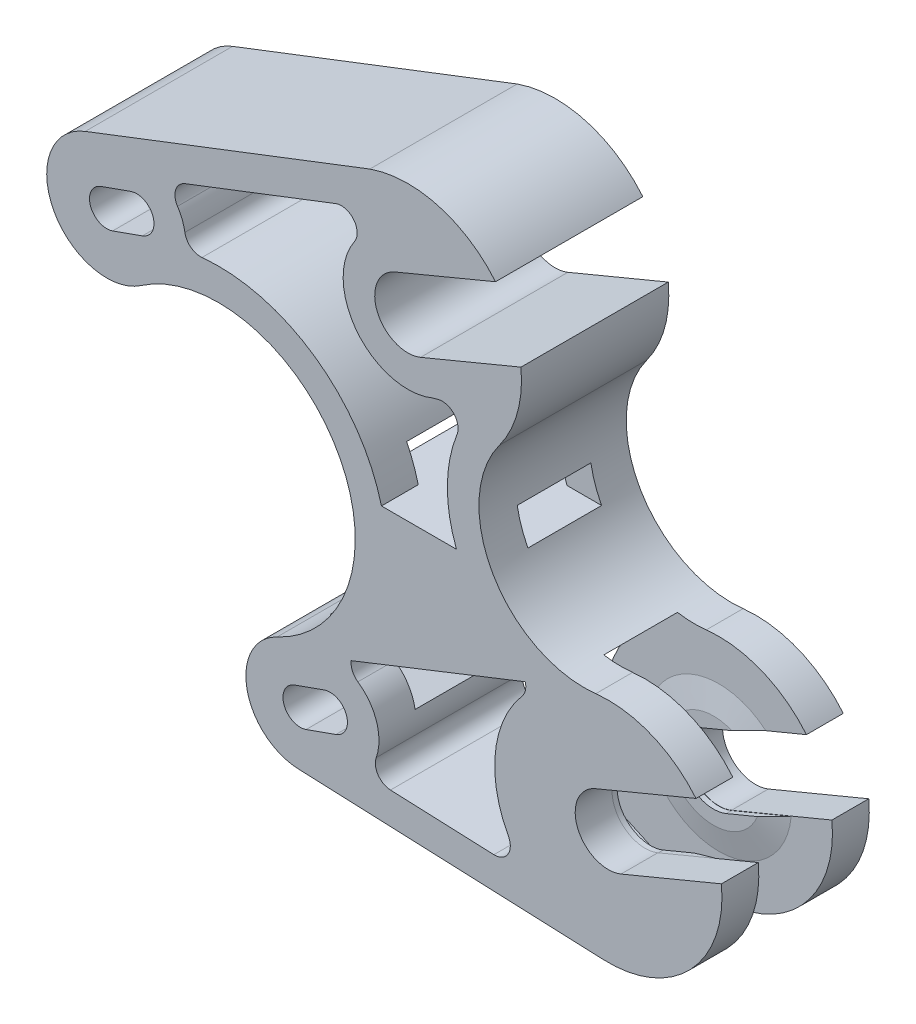
SolidWorks part; units mm, degrees
material "ABS"
ref_plane "Front Plane" through (0, 0, 0) normal (0, 0, 1) x (1, 0, 0)
ref_plane "Top Plane" through (0, 0, 0) normal (0, 1, 0) x (1, 0, 0)
ref_plane "Right Plane" through (0, 0, 0) normal (1, 0, 0) x (0, 0, -1)
ref_plane "Plane1" through (0, 0, 7) normal (0, 0, 1) x (1, 0, 0)
sketch "Sketch1" plane through (0, 0, 0) normal (0, 0, 1) x (1, 0, 0)
  line L0 (18, 21) -> (37.0525, -11.9999) construction
  line L1 (15.9217, 9.1924) -> (-6.382, 15.1686) construction
  line L2 (-9.1924, 15.9217) -> (-15.9217, -9.1924) construction
  line L3 (-15.9217, -9.1924) -> (7.5986, -15.4946) construction
  line L4 (9.1924, -15.9217) -> (9.6194, -14.3279) construction
  line L5 (0, 0) -> (50.7667, 0) construction
  line L6 (0, 0) -> (-9.1924, 15.9217) construction
  line L7 (14.3863, 31.1775) -> (-12.6613, 20.7525)
  line L9 (0, 0) -> (9.1924, -15.9217) construction
  line L10 (10.0538, -13.8649) -> (7.2268, -14.8687)
  line L11 (16.7912, 23.9088) -> (26.3307, 27.8731)
  line L12 (19.2088, 18.0912) -> (28.7483, 22.0554)
  line L13 (35.8437, -9.0911) -> (45.3832, -5.1268)
  line L14 (38.2613, -14.9087) -> (47.8008, -10.9445)
  line L15 (-11.158, 16.9747) -> (-8.3309, 17.9785)
  line L16 (-10.0538, 13.8649) -> (-7.2268, 14.8687)
  line L17 (-7.5986, 15.4946) -> (-9.1924, 15.9217) construction
  line L18 (7.5655, -21.5918) -> (36.607, -22.7907)
  line L19 (11.158, -16.9747) -> (8.3309, -17.9785)
  line L20 (9.7109, -13.9867) -> (15.9217, 9.1924) construction
  arc A0 (5.5647, -11.7488) -> (-7.3672, 10.711) centre (0, 0) ccw
  arc A1 (16.7912, 23.9088) -> (19.2088, 18.0912) centre (18, 21) ccw
  arc A2 (-11.158, 16.9747) -> (-10.0538, 13.8649) centre (-10.6059, 15.4198) ccw
  arc A3 (8.3309, -17.9785) -> (7.2268, -14.8687) centre (7.7788, -16.4236) cw
  arc A4 (-12.6613, 20.7525) -> (-7.3672, 10.711) centre (-10.6059, 15.4198) ccw
  arc A5 (26.6989, 14.5993) -> (28.7483, 22.0554) centre (18, 21) ccw
  arc A6 (35.8437, -9.0911) -> (38.2613, -14.9087) centre (37.0525, -11.9999) ccw
  arc A7 (5.5647, -11.7488) -> (7.5655, -21.5918) centre (7.7788, -16.4236) ccw
  arc A8 (45.3832, -5.1268) -> (35.8587, -1.2661) centre (37.0525, -11.9999) ccw
  arc A9 (36.607, -22.7907) -> (47.8008, -10.9445) centre (37.0525, -11.9999) ccw
  arc A12 (26.6989, 14.5993) -> (35.8587, -1.2661) centre (34.7534, 8.6726) ccw
  arc A13 (26.3307, 27.8731) -> (14.3863, 31.1775) centre (18, 21) ccw
  arc A14 (-8.3309, 17.9785) -> (-7.2268, 14.8687) centre (-7.7788, 16.4236) cw
  arc A15 (10.0538, -13.8649) -> (11.158, -16.9747) centre (10.6059, -15.4198) cw
  dimension "D1" = 26
  dimension "D2" = 3
  dimension "D3" = 6.3
  dimension "D10" = 10.8
  dimension "D11" = 10
  dimension "D4" = 21
  dimension "D5" = 38.105
  dimension "D6" = 60
  dimension "D7" = 18
  dimension "D8" = 15
  dimension "D14" = 3
extrude "Boss-Extrude1" add sketch "Sketch1" along normal blind 14
sketch "Sketch3" plane through (0, 0, 7) normal (0, 0, 1) x (1, 0, 0)
  line L0 (0, 7) -> (37.0525, 7)
  line L1 (-2.9117, -6.3657) -> (32.2689, -22.4578)
  line L2 (5.7446, 4) -> (37.0525, 4)
  line L3 (3.5601, -6.0271) -> (26.4728, -16.5076)
  line L4 (37.0525, 4) -> (37.0525, 7)
  line L5 (0, 4) -> (23.3288, 4) construction
  line L6 (-1.6639, -3.6375) -> (33.5168, -19.7296) construction
  line L7 (0, 7) -> (23.3288, 7) construction
  circle A0 centre (37.0525, -11.9999) radius 9.5 construction
  arc A1 (32.2689, -22.4578) -> (26.4728, -16.5076) centre (37.0525, -11.9999) ccw
  arc A2 (35.8437, -9.0911) -> (38.2613, -14.9087) centre (37.0525, -11.9999) ccw construction
  circle A3 centre (0, 0) radius 5 construction
  arc A4 (0, 7) -> (-2.9117, -6.3657) centre (0, 0) ccw
  arc A6 (3.5601, -6.0271) -> (5.7446, 4) centre (0, 0) ccw
  dimension "D1" = 19
  dimension "D2" = 2
  dimension "D3" = 10
  dimension "D4" = 2
  dimension "D5" = 3
  dimension "D6" = 3
extrude "Cut-Extrude1" cut sketch "Sketch3" against normal blind 3.5 and the other way blind 3.5
sketch "Sketch4" plane through (0, 0, 14) normal (0, 0, 1) x (1, 0, 0)
  line L2 (7.6892, -18.5944) -> (36.7308, -19.7933)
  line L4 (15.4653, 28.3782) -> (-11.5824, 17.9532)
  line L5 (16.3482, -18.9518) -> (26.1757, -19.3575)
  line L6 (20.8827, 15.4616) -> (20.36, 15.3209)
  line L8 (11.1417, 26.7118) -> (-3.1743, 21.194)
  arc A0 (36.607, -22.7907) -> (47.8008, -10.9445) centre (37.0525, -11.9999) ccw construction
  arc A1 (14.9944, -16.9572) -> (16.3482, -18.9518) centre (16.4101, -17.4531) ccw
  arc A2 (12.9201, 24.4666) -> (11.1417, 26.7118) centre (11.6812, 25.3122) ccw
  arc A3 (22.6673, 13.4607) -> (20.8827, 15.4616) centre (21.2727, 14.0132) ccw
  arc A4 (28.8481, -4.9765) -> (28.4374, -2.6899) centre (27.7086, -4.001) ccw
  arc A5 (-3.1743, 21.194) -> (-3.8895, 18.9722) centre (-2.6349, 19.7943) ccw
  arc A6 (-3.1898, 17.1742) -> (-1.563, 15.9235) centre (-1.7095, 17.4163) ccw
  arc A7 (12.8944, -9.4729) -> (13.2502, -11.5948) centre (14.1032, -10.361) ccw
  arc A8 (33.1202, -1.1931) -> (26.4728, -16.5076) centre (37.0525, -11.9999) ccw construction
  arc A9 (26.1757, -19.3575) -> (27.5564, -17.1443) centre (26.2375, -17.8588) ccw
  arc A11 (33.1202, -1.1931) -> (29.5838, -3.2553) centre (37.0525, -11.9999) ccw construction
  arc A14 (15.64, 26.6791) -> (20.36, 15.3209) centre (18, 21) ccw
  arc A15 (12.9201, 24.4666) -> (20.36, 15.3209) centre (18, 21) ccw
  arc A17 (24.2825, 16.3772) -> (36.1903, -4.2477) centre (34.7534, 8.6726) ccw
  arc A18 (22.6673, 13.4607) -> (28.4374, -2.6899) centre (34.7534, 8.6726) ccw
  arc A20 (-6.223, 12.0416) -> (-9.3347, 20.8056) centre (-7.7788, 16.4236) ccw
  arc A21 (-3.1898, 17.1742) -> (-3.8895, 18.9722) centre (-7.7788, 16.4236) ccw
  arc A23 (6.8488, -14.4601) -> (-9.0673, 13.1827) centre (0, 0) ccw
  arc A24 (12.8944, -9.4729) -> (-1.563, 15.9235) centre (0, 0) ccw
  arc A26 (12.1618, -19.8018) -> (9.05, -11.0378) centre (10.6059, -15.4198) ccw
  arc A27 (14.9944, -16.9572) -> (13.2502, -11.5948) centre (10.6059, -15.4198) ccw
  arc A29 (28.8481, -4.9765) -> (27.5564, -17.1443) centre (37.0525, -11.9999) ccw
  dimension "D1" = 3
  dimension "D2" = 3
  dimension "D3" = 3
  dimension "D4" = 3
  dimension "D8" = 10.8
  dimension "D9" = 1.5
  dimension "D10" = 3
  dimension "D11" = 3
  dimension "D12" = 3
  dimension "D13" = 3
  dimension "D14" = 3
  dimension "D15" = 3
  dimension "D16" = 3
  dimension "D5" = 3
  dimension "D6" = 3
  dimension "D7" = 3
extrude "Cut-Extrude2" cut sketch "Sketch4" against normal through all
sketch "Sketch5" plane through (0, 0, 3.5) normal (0, 0, 1) x (1, 0, 0)
  line L0 (35.8356, -9.0715) -> (38.7839, -7.8463)
  line L1 (38.2694, -14.9283) -> (41.2177, -13.7031)
  line L2 (47.8008, -10.9445) -> (38.2613, -14.9087) construction
  line L3 (35.8437, -9.0911) -> (45.3832, -5.1268) construction
  line L7 (37.0525, -11.9999) -> (43.022, -20.3936) construction
  line L8 (37.0525, -11.9999) -> (32.7681, -21.3665) construction
  arc A0 (35.8356, -9.0715) -> (38.2694, -14.9283) centre (37.0525, -11.9999) ccw
  arc A1 (38.7839, -7.8463) -> (41.2177, -13.7031) centre (37.0525, -11.9999) ccw
  dimension "D1" = 4.5
extrude "Boss-Extrude2" add sketch "Sketch5" along normal blind 0.5
chamfer "Chamfer1" distance 2.4 distance2 0.5 1 edges at (32.897, -13.7268, 3.5) first distance on face at (33.8599, -12.6808, 3.5)
mirror "Mirror2" about plane through (0, 0, 7) normal (0, 0, 1) of "Boss-Extrude2"
chamfer "Chamfer3" distance 0.5 distance2 2.4 1 edges at (32.897, -13.7268, 10.5) first distance on face at (36.4489, -12.2507, 10.25)
sketch "Sketch8" [suppressed] plane through (-0.6239, -1.3641, 0) normal (0.416, 0.9094, 0) x (0.9094, -0.416, 0)
  line L0 (43.1826, -4) -> (31.2541, -4)
  line L1 (31.2541, -4) -> (31.2541, -3.5)
  line L2 (30.6152, -3.5) -> (33.1359, -3.5) construction
  line L3 (31.2541, -3.5) -> (-32.8331, -3.5)
  line L4 (-32.8331, -3.5) -> (-32.8331, -21.3425)
  line L5 (-32.8331, -21.3425) -> (57.2454, -20.1119)
  line L6 (57.2454, -20.1119) -> (57.2454, -4.2941)
  line L7 (57.2454, -4.2941) -> (43.1826, -4)
sketch "Sketch9" plane through (0, 0, 0) normal (0, 0, -1) x (-1, 0, 0)
  line L0 (-22.6222, 4) -> (-15.4919, 4)
  line L1 (-29.1628, -3.6331) -> (-12.6155, -10.1691)
  arc A7 (-28.4374, -2.6899) -> (-28.8481, -4.9765) centre (-27.7086, -4.001) ccw construction
  arc A10 (-28.4374, -2.6899) -> (-22.6673, 13.4607) centre (-34.7534, 8.6726) ccw construction
  arc A11 (-28.4374, -2.6899) -> (-29.1628, -3.6331) centre (-27.7086, -4.001) ccw
  arc A13 (-28.4374, -2.6899) -> (-22.6222, 4) centre (-34.7534, 8.6726) ccw
  arc A14 (1.563, 15.9235) -> (-12.8944, -9.4729) centre (0, 0) ccw construction
  arc A15 (-15.4919, 4) -> (-12.8944, -9.4729) centre (0, 0) ccw
  arc A16 (-13.2502, -11.5948) -> (-12.8944, -9.4729) centre (-14.1032, -10.361) ccw construction
  arc A17 (-12.6155, -10.1691) -> (-12.8944, -9.4729) centre (-14.1032, -10.361) ccw
extrude "Boss-Extrude3" add sketch "Sketch9" against normal up to surface (14 mm away) up to face at (14.4975, 4.0726, 14)
sketch "Sketch10" plane through (0, 0, 3.5) normal (0, 0, 1) x (1, 0, 0)
  line L0 (33.1202, -1.1931) -> (28.6155, -12.5695)
  line L1 (28.6155, -12.5695) -> (39.2733, -25.7831)
  line L2 (39.2733, -25.7831) -> (-28.8535, -31.5682)
  line L3 (-28.8535, -31.5682) -> (-50.4034, 29.9611)
  line L4 (-50.4034, 29.9611) -> (-45.527, 33.8943)
  line L5 (15.1425, 58.5222) -> (-45.527, 33.8943)
  line L6 (15.1425, 58.5222) -> (49.5372, 15.8796)
  line L7 (49.5372, 15.8796) -> (33.1202, -1.1931)
extrude "Cut-Extrude3" [suppressed] cut sketch "Sketch10" along normal through all
sketch "Sketch11" plane through (0, 0, 14) normal (0, 0, 1) x (1, 0, 0)
  line L4 (16.7912, 23.9088) -> (26.3307, 27.8731)
  line L5 (16.7912, 23.9088) -> (26.3307, 27.8731)
  line L6 (47.8008, -10.9445) -> (38.2613, -14.9087)
  line L7 (35.8437, -9.0911) -> (45.3832, -5.1268)
  line L8 (14.3863, 31.1775) -> (-12.6613, 20.7525)
  line L9 (14.3863, 31.1775) -> (-12.6613, 20.7525)
  line L10 (47.8008, -10.9445) -> (38.2613, -14.9087)
  line L11 (35.8437, -9.0911) -> (45.3832, -5.1268)
  line L14 (7.5655, -21.5918) -> (36.607, -22.7907)
  line L15 (7.5655, -21.5918) -> (36.607, -22.7907)
  line L16 (28.7483, 22.0554) -> (19.2088, 18.0912)
  line L17 (28.7483, 22.0554) -> (19.2088, 18.0912)
  arc A4 (36.607, -22.7907) -> (47.8008, -10.9445) centre (37.0525, -11.9999) ccw
  arc A5 (35.8437, -9.0911) -> (38.2613, -14.9087) centre (37.0525, -11.9999) ccw
  arc A6 (45.3832, -5.1268) -> (35.8587, -1.2661) centre (37.0525, -11.9999) ccw
  arc A7 (26.6989, 14.5993) -> (35.8587, -1.2661) centre (34.7534, 8.6726) ccw
  arc A8 (36.607, -22.7907) -> (47.8008, -10.9445) centre (37.0525, -11.9999) ccw
  arc A9 (35.8437, -9.0911) -> (38.2613, -14.9087) centre (37.0525, -11.9999) ccw
  arc A10 (45.3832, -5.1268) -> (35.8587, -1.2661) centre (37.0525, -11.9999) ccw
  arc A11 (26.6989, 14.5993) -> (35.8587, -1.2661) centre (34.7534, 8.6726) ccw
  arc A18 (16.7912, 23.9088) -> (19.2088, 18.0912) centre (18, 21) ccw
  arc A19 (16.7912, 23.9088) -> (19.2088, 18.0912) centre (18, 21) ccw
  arc A20 (26.3307, 27.8731) -> (14.3863, 31.1775) centre (18, 21) ccw
  arc A21 (26.3307, 27.8731) -> (14.3863, 31.1775) centre (18, 21) ccw
  arc A22 (-12.6613, 20.7525) -> (-7.3672, 10.711) centre (-10.6059, 15.4198) ccw
  arc A23 (-12.6613, 20.7525) -> (-7.3672, 10.711) centre (-10.6059, 15.4198) ccw
  arc A24 (5.5647, -11.7488) -> (-7.3672, 10.711) centre (0, 0) ccw
  arc A25 (5.5647, -11.7488) -> (-7.3672, 10.711) centre (0, 0) ccw
  arc A26 (5.5647, -11.7488) -> (7.5655, -21.5918) centre (7.7788, -16.4236) ccw
  arc A27 (5.5647, -11.7488) -> (7.5655, -21.5918) centre (7.7788, -16.4236) ccw
  arc A28 (26.6989, 14.5993) -> (28.7483, 22.0554) centre (18, 21) ccw
  arc A29 (26.6989, 14.5993) -> (28.7483, 22.0554) centre (18, 21) ccw
  dimension "D1" = 0
extrude "Cut-Extrude4" [suppressed] cut sketch "Sketch11" against normal up to surface (4 mm away)
sketch "Sketch12" plane through (0, 0, 3.5) normal (0, 0, 1) x (1, 0, 0)
  line L1 (-70.4462, 47.4477) -> (118.5322, 47.4477)
  line L2 (-70.4462, 47.4477) -> (-70.4462, -36.5289)
  line L3 (-70.4462, -36.5289) -> (118.5322, -36.5289)
  line L4 (118.5322, 47.4477) -> (118.5322, -36.5289)
  line L5 (-70.4462, 47.4477) -> (118.5322, -36.5289) construction
  line L6 (-70.4462, -36.5289) -> (118.5322, 47.4477) construction
  point P0 (24.043, 5.4594)
extrude "Cut-Extrude5" [suppressed] cut sketch "Sketch12" against normal blind 10
sketch "Sketch14" [suppressed] plane through (0, 0, 3.5) normal (0, 0, -1) x (-1, 0, 0)
  line L2 (-38.2694, -14.9283) -> (-43.9284, -12.5766)
  line L3 (-41.4945, -6.7199) -> (-35.8356, -9.0715)
  line L4 (-38.2694, -14.9283) -> (-43.9284, -12.5766)
  line L5 (-41.4945, -6.7199) -> (-35.8356, -9.0715)
  arc A2 (-43.9284, -12.5766) -> (-41.4945, -6.7199) centre (-37.0525, -11.9999) ccw
  arc A3 (-38.2694, -14.9283) -> (-35.8356, -9.0715) centre (-37.0525, -11.9999) ccw
  arc A4 (-43.9284, -12.5766) -> (-41.4945, -6.7199) centre (-37.0525, -11.9999) ccw
  arc A5 (-38.2694, -14.9283) -> (-35.8356, -9.0715) centre (-37.0525, -11.9999) ccw
  dimension "D1" = 0
extrude "Cut-Extrude6" [suppressed] cut sketch "Sketch14" against normal up to next
chamfer "Chamfer4" [suppressed] distance 0.5 angle 45
chamfer "Chamfer5" [suppressed] distance 0.5 angle 45
